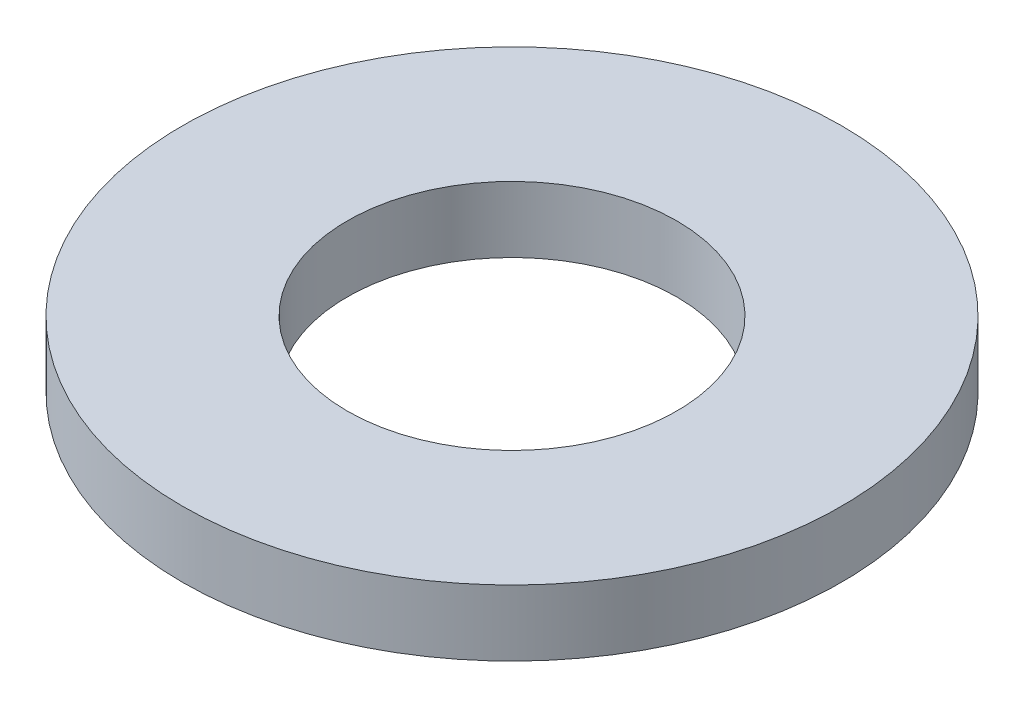
SolidWorks part; units mm, degrees
ref_plane "Front Plane" through (0, 0, 0) normal (0, 0, 1) x (1, 0, 0)
ref_plane "Top Plane" through (0, 0, 0) normal (0, 1, 0) x (1, 0, 0)
ref_plane "Right Plane" through (0, 0, 0) normal (1, 0, 0) x (0, 0, -1)
sketch "Sketch1" plane through (0, 0, 0) normal (0, 1, 0) x (1, 0, 0)
  circle A0 centre (0, 0) radius 75
  dimension "FLANGE_OD" = 150
extrude "Boss-Extrude1" add sketch "Sketch1" along normal blind 15
sketch "Sketch2" plane through (0, 0, 0) normal (0, 1, 0) x (1, 0, 0)
  circle A0 centre (0, 0) radius 37.5
  dimension "BORE_D" = 75
extrude "Cut-Extrude1" cut sketch "Sketch2" along normal through all
sketch "Sketch3" plane through (0, 15, 0) normal (0, 1, 0) x (1, 0, 0)
  circle A0 centre (0, 0) radius 25.5663 construction
  circle A1 centre (-25.5663, 0) radius 2.2375
  dimension "BOLT_D" = 4.475
  dimension "BOLT_PCD" = 51.1326
extrude "Cut-Extrude2" cut sketch "Sketch3" against normal blind 14.6422 rebuild error yes
pattern_circular "CirPattern1" count 3 over 360 rebuild error yes
